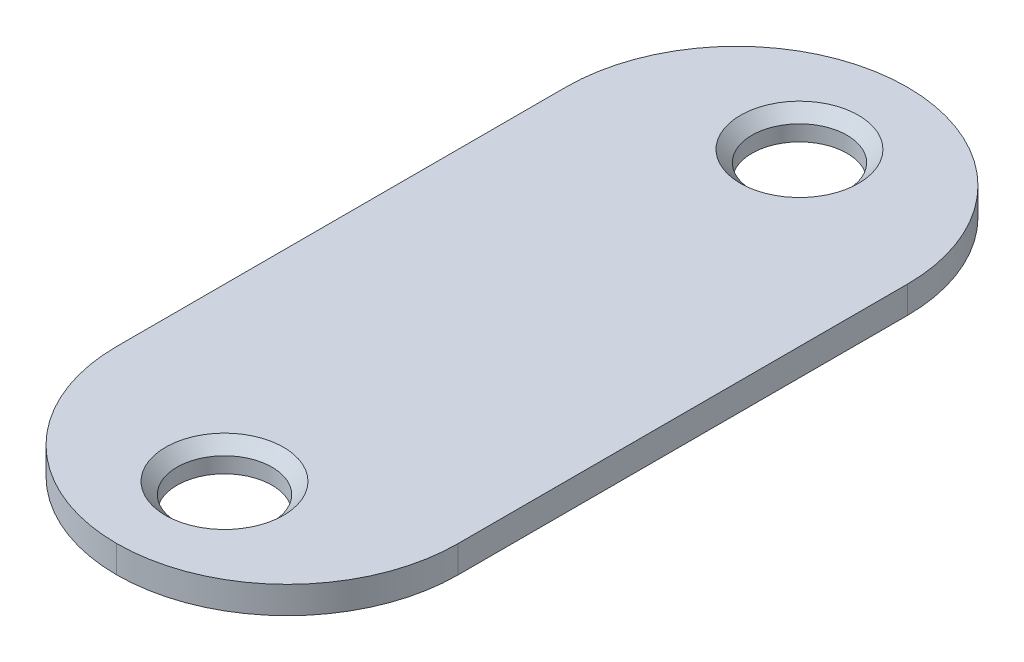
SolidWorks part; units mm, degrees
ref_plane "Front" through (0, 0, 0) normal (0, 0, 1) x (1, 0, 0)
ref_plane "Top" through (0, 0, 0) normal (0, 1, 0) x (1, 0, 0)
ref_plane "Right" through (0, 0, 0) normal (1, 0, 0) x (0, 0, -1)
sketch "Sketch1" plane through (0, 0, 0) normal (0, 1, 0) x (1, 0, 0)
  line L0 (0, 17.4625) -> (0, -17.4625) construction
  line L1 (-7.5406, 17.4625) -> (7.5406, 17.4625)
  line L2 (-7.5406, 17.4625) -> (-7.5406, -17.4625)
  line L3 (-7.5406, -17.4625) -> (7.5406, -17.4625)
  line L4 (7.5406, 17.4625) -> (7.5406, -17.4625)
  dimension "D1" = 15.0812
  dimension "D2" = 34.925
extrude "Extrude1" add sketch "Sketch1" along normal blind 1.2
sketch "Sketch3" plane through (0, 1.2, 0) normal (0, 1, 0) x (1, 0, 0)
  line L0 (0, 12.7) -> (0, -12.7) construction
  circle A0 centre (0, 12.7) radius 2.1
  circle A1 centre (0, -12.7) radius 2.1
  dimension "D2" = 4.2
  dimension "D1" = 25.4
extrude "Extrude2" cut sketch "Sketch3" against normal blind 1.9844
chamfer "Chamfer1" distance 0.508 angle 45 2 edges at (0, 1.2, 14.8) (0, 1.2, -10.6)
fillet "Fillet1" radius 7.5406 1 edges at (-7.5406, 0.6, -17.4625)
fillet "Fillet2" radius 7.5406 3 edges at (7.5406, 0.6, 17.4625) (-7.5406, 0.6, 17.4625) (7.5406, 0.6, -17.4625)
